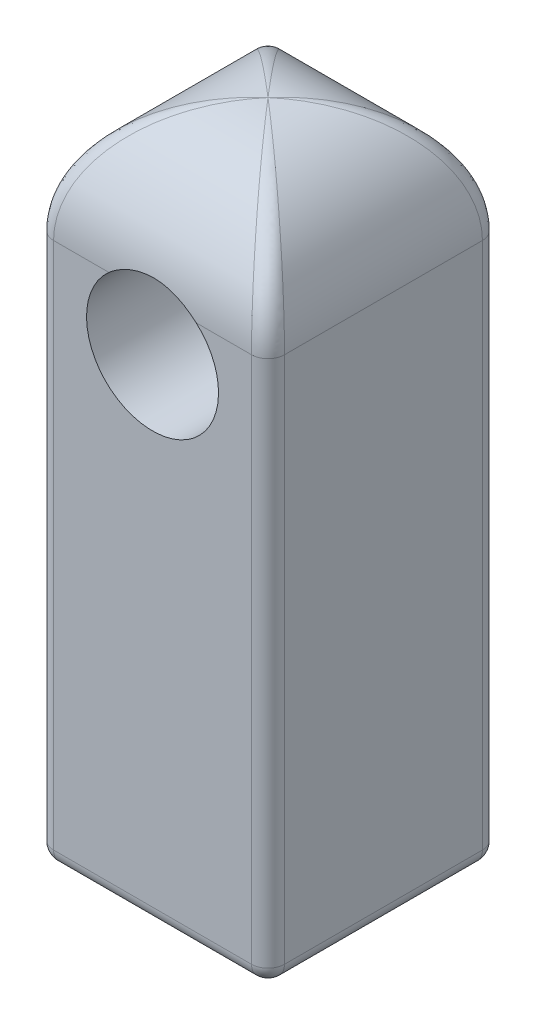
SolidWorks part; units mm, degrees
material "ABS PC"
ref_plane "Front Plane" through (0, 0, 0) normal (0, 0, 1) x (1, 0, 0)
ref_plane "Top Plane" through (0, 0, 0) normal (0, 1, 0) x (1, 0, 0)
ref_plane "Right Plane" through (0, 0, 0) normal (1, 0, 0) x (0, 0, -1)
sketch "Sketch1" plane through (0, 0, 0) normal (0, 0, 1) x (1, 0, 0)
  line L0 (0, 5) -> (0, -15) construction
  line L1 (-3.5, 5) -> (3.5, 5)
  line L2 (-3.5, 5) -> (-3.5, -15)
  line L3 (-3.5, -15) -> (3.5, -15)
  line L4 (3.5, 5) -> (3.5, -15)
  circle A0 centre (0, 0) radius 2
  dimension "D4" = 4
  dimension "D1" = 7
  dimension "D2" = 20
  dimension "D3" = 5
extrude "Boss-Extrude1" add sketch "Sketch1" along normal mid plane 7
fillet "Fillet1" radius 3.5 4 edges at (0, 5, -3.5) (0, 5, 3.5) (3.5, 5, 0) (-3.5, 5, 0)
fillet "Fillet2" radius 0.5 12 edges at (3.5, -15, 0) (3.5, -6.75, 3.5) (3.5, -6.75, -3.5) (-3.5, -6.75, 3.5) (-3.5, -15, 0) (-3.5, -6.75, -3.5) (0, -15, 3.5) (0, -15, -3.5) (2.4749, 3.9749, 2.4749) (-2.4749, 3.9749, -2.4749) (2.4749, 3.9749, -2.4749) (-2.4749, 3.9749, 2.4749)
